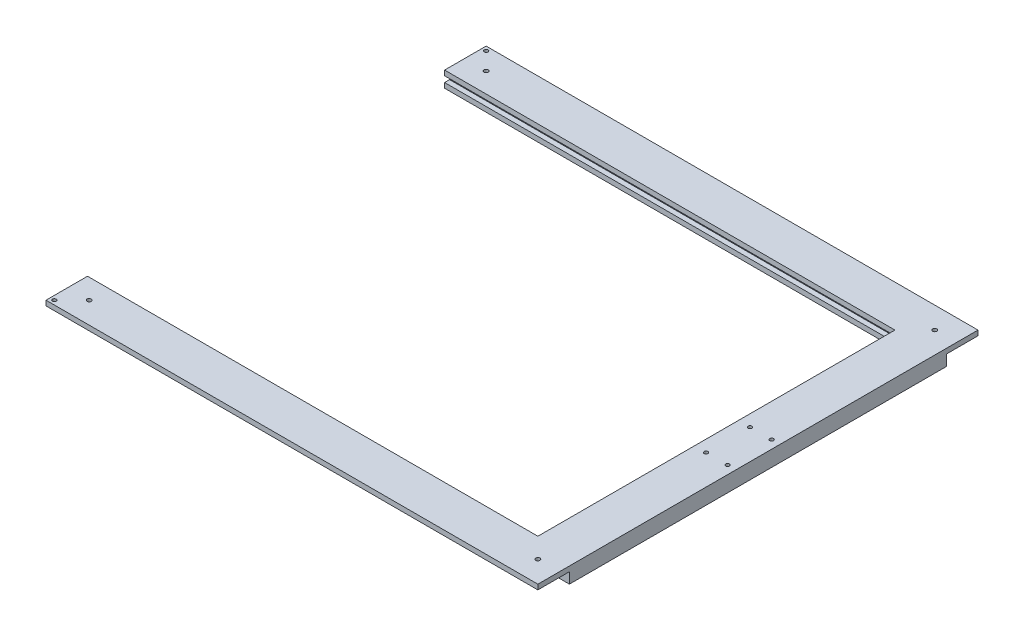
SolidWorks part; units mm, degrees
ref_plane "Спереди" through (0, 0, 0) normal (0, 0, 1) x (1, 0, 0)
ref_plane "Сверху" through (0, 0, 0) normal (0, 1, 0) x (1, 0, 0)
ref_plane "Справа" through (0, 0, 0) normal (1, 0, 0) x (0, 0, -1)
sketch "Эскиз1" plane through (0, 0, 0) normal (0, 1, 0) x (1, 0, 0)
  line L0 (50, -77.9215) -> (50, -607.9215)
  line L1 (-542.3, -77.9215) -> (50, -77.9215)
  line L2 (-542.3, -77.9215) -> (-542.3, -127.9215)
  line L3 (-542.3, -607.9215) -> (50, -607.9215)
  line L5 (-542.3, -127.9215) -> (0, -127.9215)
  line L7 (-542.3, -557.9215) -> (0, -557.9215)
  line L13 (-542.3, -557.9215) -> (-542.3, -607.9215)
  line L22 (0, -127.9215) -> (0, -557.9215)
  dimension "D1" = 592.3
  dimension "D12" = 50
  dimension "D2" = 530
  dimension "D3" = 50
  dimension "D4" = 50
  dimension "D9" = 50
  dimension "D8" = 77.9215
extrude "Бобышка-Вытянуть2" add sketch "Эскиз1" along normal blind 6
sketch "Эскиз2" plane through (0, 0, 0) normal (0, -1, 0) x (1, 0, 0)
  line L0 (-542.3, 127.9215) -> (0, 127.9215) construction
  line L5 (50, 607.9215) -> (50, 77.9215) construction
  line L6 (0, 557.9215) -> (-542.3, 557.9215) construction
  line L18 (50, 569.9215) -> (50, 115.9215)
  line L20 (6, 563.9215) -> (6, 121.9215)
  line L21 (-542.3, 77.9215) -> (-542.3, 127.9215) construction
  line L22 (50, 115.9215) -> (-542.3, 115.9215)
  line L24 (6, 121.9215) -> (-542.3, 121.9215)
  line L25 (-542.3, 115.9215) -> (-542.3, 121.9215)
  line L26 (-542.3, 557.9215) -> (-542.3, 607.9215) construction
  line L27 (50, 569.9215) -> (-542.3, 569.9215)
  line L29 (6, 563.9215) -> (-542.3, 563.9215)
  line L30 (-542.3, 569.9215) -> (-542.3, 563.9215)
  dimension "D1" = 44
  dimension "D2" = 6
  dimension "D3" = 6
  dimension "D4" = 6
  dimension "D5" = 6
extrude "Бобышка-Вытянуть3" add sketch "Эскиз2" along normal blind 7
sketch "Эскиз4" plane through (0, 6, 0) normal (0, 1, 0) x (1, 0, 0)
  line L0 (50, -77.9215) -> (-542.3, -77.9215) construction
  line L1 (-542.3, -77.9215) -> (-542.3, -127.9215) construction
  circle A0 centre (-516.3, -103.9215) radius 2.5
  dimension "D1" = 5
  dimension "D2" = 26
  dimension "D3" = 26
extrude "Вырез-Вытянуть1" cut sketch "Эскиз4" against normal through all
pattern_linear "Линейный массив2" count 2 spacing 540.3 along (1, 0, 0) count 2 spacing 478 along (0, 0, 1) of "Вырез-Вытянуть1"
sketch "Эскиз5" plane through (0, -7, 0) normal (0, -1, 0) x (1, 0, 0)
  line L8 (50, 569.9215) -> (-542.3, 569.9215)
  line L9 (-542.3, 569.9215) -> (-542.3, 557.9215)
  line L10 (-542.3, 557.9215) -> (0, 557.9215)
  line L11 (0, 557.9215) -> (0, 127.9215)
  line L12 (0, 127.9215) -> (-542.3, 127.9215)
  line L13 (-542.3, 127.9215) -> (-542.3, 115.9215)
  line L14 (-542.3, 115.9215) -> (50, 115.9215)
  line L15 (50, 115.9215) -> (50, 569.9215)
extrude "Бобышка-Вытянуть4" add sketch "Эскиз5" along normal blind 6
sketch "Эскиз6" plane through (0, -13, 0) normal (0, -1, 0) x (1, 0, 0)
  line L0 (40, 342.9215) -> (50, 342.9215) construction
  line L1 (40, 316.4215) -> (14, 316.4215) construction
  line L2 (40, 316.4215) -> (40, 369.4215) construction
  line L3 (40, 369.4215) -> (14, 369.4215) construction
  line L4 (14, 316.4215) -> (14, 369.4215) construction
  line L5 (50, 115.9215) -> (50, 569.9215) construction
  circle A1 centre (14, 369.4215) radius 2.25
  circle A2 centre (40, 369.4215) radius 2.25
  circle A3 centre (40, 316.4215) radius 2.25
  circle A4 centre (14, 316.4215) radius 2.25
  point P4 (50, 342.9215)
  point P6 (40, 342.9215)
  dimension "D4" = 4.5
  dimension "D1" = 53
  dimension "D2" = 26
  dimension "D3" = 10
extrude "Вырез-Вытянуть2" cut sketch "Эскиз6" against normal through all
sketch "Эскиз7" plane through (0, 0, 0) normal (0, -1, 0) x (1, 0, 0)
  line L0 (-542.3, 597.9215) -> (-532.3, 607.9215) construction
  line L1 (-542.3, 607.9215) -> (-532.3, 607.9215) construction
  line L2 (-542.3, 607.9215) -> (-542.3, 597.9215) construction
  line L3 (-542.3, 597.9215) -> (-532.3, 597.9215) construction
  line L4 (-532.3, 607.9215) -> (-532.3, 597.9215) construction
  line L5 (-542.3, 607.9215) -> (-532.3, 597.9215) construction
  line L6 (-532.3, 87.9215) -> (-542.3, 77.9215) construction
  line L7 (-542.3, 77.9215) -> (-532.3, 77.9215) construction
  line L8 (-542.3, 77.9215) -> (-542.3, 87.9215) construction
  line L9 (-542.3, 87.9215) -> (-532.3, 87.9215) construction
  line L10 (-532.3, 77.9215) -> (-532.3, 87.9215) construction
  line L11 (-542.3, 87.9215) -> (-532.3, 77.9215) construction
  circle A0 centre (-537.3, 602.9215) radius 2.25
  circle A1 centre (-537.3, 82.9215) radius 2.25
  point P12 (-537.3, 82.9215)
  dimension "D3" = 4.5
  dimension "D6" = 4.5
  dimension "D1" = 10
  dimension "D2" = 10
  dimension "D4" = 10
  dimension "D5" = 10
extrude "Вырез-Вытянуть3" cut sketch "Эскиз7" against normal through all
equation "\"Ширина груза\"= 420"
equation "\"Глубина груза\"= 490"
equation "\"Высота груза\"= 297"
equation "\"Ширина ячейки\"= \"Ширина груза\" + 10"
equation "\"Глубина ячейки\"= \"Глубина груза\" + 10"
equation "\"Высота ячейки\"= \"Высота груза\" + 10 + 13"
equation "\"Колво ячеек ширина\"= 2"
equation "\"Колво ячеек высота\"= 2"
equation "\"Толщина стенки\" = \"Толщина тонких панелей\""
equation "\"Крепление дверцы\"= 5 "
equation "\"Ширина рейки\"= \"Толщина шестерни\""
equation "\"Высота рейки\"= 20"
equation "\"Высота пола\" = 2*\"Толщина тонких панелей\""
equation "\"Колво полозьев\"= 5"
equation "\"Отступ рейки\"= 20"
equation "\"Глубина каретки\"= \"Глубина ячейки\" + 30 + \"Мотор Y высота корпуса\" + 20"
equation "\"Длинна рейки\" = (\"Ширина ячейки\"+\"Толщина вертикальных стенок\"+\"Крепление дверцы\")*\"Колво ячеек ширина\"+\"Ширина ячейки выгрузки\"*\"Колво выгрузки\"+\"Толщина вертикальных стенок\"+2*\"Отступ крепления мотора фиксации\"-\"Крепление дверцы\"*\"Колво ячеек ширина\""
equation "\"Отступ шпильки\"= 26"
equation "\"Диаметр шпильки\"= 5"
equation "\"Длинна шпильки\" = (\"Высота ячейки\"+\"Толщина горизонтальных плит\"+\"Высота пола\")*\"Колво ячеек высота\"+2*(\"Толщина горизонтальных плит\"+\"Отступ рейки\")"
equation "\"D2@Эскиз1\"=\"Ширина ячейки\" + \"Ширина пластины\" * 2 "
equation "\"D9@Эскиз1\"=\"Ширина пластины\""
equation "\"D3@Эскиз1\"=\"Ширина пластины\""
equation "\"D4@Эскиз1\"= \"Ширина пластины\""
equation "\"Ширина пластины\"= 50  "
equation "\"D1@Бобышка-Вытянуть2\"=\"Толщина стенки\""
equation "\"D1@Эскиз4\"= \"Диаметр шпильки\""
equation "\"D4@Линейный массив2\"=\"Ширина ячейки\" + \"Ширина пластины\" * 2  - \"Отступ шпильки\" * 2"
equation "\"D1@Эскиз1\"= \"Глубина каретки\""
equation "\"D3@Линейный массив2\"= \"Глубина каретки\" - \"Отступ шпильки\" * 2"
equation "\"D2@Эскиз4\"=\"Отступ шпильки\""
equation "\"D3@Эскиз4\"= \"Отступ шпильки\""
equation "\"D1@Эскиз2\"= \"Ширина пластины\" - \"Толщина стенки\""
equation "\"D2@Эскиз2\"= \"Толщина стенки\""
equation "\"D3@Эскиз2\"= \"Толщина стенки\""
equation "\"D4@Эскиз2\"= \"Толщина стенки\""
equation "\"D5@Эскиз2\"= \"Толщина стенки\""
equation "\"D1@Бобышка-Вытянуть4\"= \"Толщина стенки\""
equation "\"Вы\"=20"
equation "\"D1@Бобышка-Вытянуть3\"=\"Высота пола\" - 5"
equation "\"Высота зона выгрузки\"= \"Высота ячейки\" * 2 + \"Толщина стенки\" * 2"
equation "\"Колво выгрузки\"= 1"
equation "\"Ширина ячейки выгрузки\" = \"Ширина ячейки\"+\"Толщина вертикальных стенок\"+2*\"Отступ крепления мотора фиксации\""
equation "\"Отступ крепления мотора фиксации\" = (\"Ширина пластины\"+20-\"Толщина вертикальных стенок\")/2"
equation "\"Мотор X ширина корпуса\"= 42.3"
equation "\"Мотор X высота корпуса\"= 42.3"
equation "\"Мотор X длина корпуса\"= 40"
equation "\"Мотор X вылет вала\"= 19.8"
equation "\"Мотор Y ширина корпуса\"= 42.3"
equation "\"Мотор Y высота корпуса\"= 42.3"
equation "\"Мотор Y длина корпуса\"= 48"
equation "\"Мотор Y вылет вала\"= 30"
equation "\"Мотор Z ширина корпуса\"= 42"
equation "\"Мотор Z высота корпуса\"= 42"
equation "\"Мотор Z длина корпуса\"= 40"
equation "\"Мотор Z вылет вала\"= 23"
equation "\"Мотор диаметр вала ПРЕДВ\"= 5"
equation "\"Мотор шаг крепления ПРЕДВ\"= 31"
equation "\"Мотор диаметр отверстий ПРЕДВ\"= 3"
equation "\"Мотор глубина отверстий ПРЕДВ\"= 4.5"
equation "\"Мотор диаметр буртика ПРЕДВ\"= 22"
equation "\"Мотор высота буртика ПРЕДВ\"= 2"
equation "\"Мотор диаметр шкива ПРЕДВ\"= 16"
equation "\"Мотор длина шкива ПРЕДВ\"= 12"
equation "\"Мотор отступ шкива ПРЕДВ\"= 5"
equation "\"Мотор X шаг градусов\"= 1.8"
equation "\"Мотор X ток А\"= 1.5"
equation "\"Мотор X сопротивление Ом\"= 1.3"
equation "\"Мотор X индуктивность мГн\"= 2"
equation "\"Мотор Y шаг градусов\"= 1.8"
equation "\"Мотор Y ток А\"= 2.2"
equation "\"Мотор Y сопротивление Ом\"= 0.9"
equation "\"Мотор Y индуктивность мГн\"= 2"
equation "\"Мотор Z шаг градусов\"= 1.8"
equation "\"Мотор Z ток А\"= 1"
equation "\"Мотор Z сопротивление Ом\"= 4"
equation "\"Мотор Z индуктивность мГн\"= 8"
equation "\"Мотор Y диаметр ротора\"= 25.78"
equation "\"Толщина тонких панелей\"= 6"
equation "\"Толщина вертикальных стенок\"= 18"
equation "\"Толщина горизонтальных плит\"= 18"
equation "\"Базовая высота корпуса\"= (\"Высота ячейки\"+\"Толщина тонких панелей\"+\"Высота пола\")*\"Колво ячеек высота\"+6*\"Толщина тонких панелей\"+\"Мотор X ширина корпуса\"+\"Мотор Y ширина корпуса\"+75"
equation "\"Высота корпуса\"= (\"Высота ячейки\"+\"Толщина горизонтальных плит\"+\"Высота пола\")*\"Колво ячеек высота\"+2*\"Толщина горизонтальных плит\"+4*\"Толщина тонких панелей\"+\"Мотор X ширина корпуса\"+\"Мотор Y ширина корпуса\"+75"
equation "\"Смещение центра корпуса\"= (\"Высота корпуса\"-\"Базовая высота корпуса\")/2-(\"Толщина горизонтальных плит\"-\"Толщина тонких панелей\")"
equation "\"Отметка пола\"= -\"Базовая высота корпуса\"/2+\"Толщина тонких панелей\""
equation "\"Отметка потолка\"= \"Отметка пола\"+\"Высота корпуса\"-2*\"Толщина горизонтальных плит\""
equation "\"Отметка верхней полки\"= \"Отметка потолка\"-(28+\"Толщина тонких панелей\")-\"Высота ячейки\"-\"Высота пола\""
equation "\"Отметка нижней полки\"= \"Отметка верхней полки\"-\"Высота ячейки\"-\"Высота пола\"-\"Толщина горизонтальных плит\""
